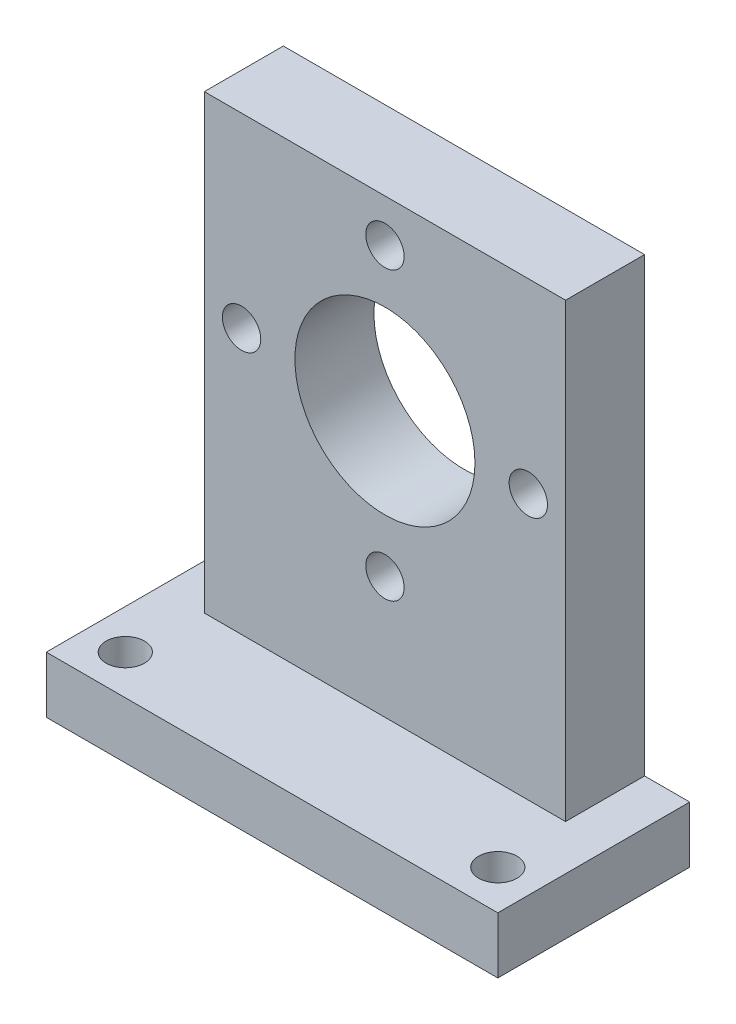
SolidWorks part; units mm, degrees
ref_plane "Front Plane" through (0, 0, 0) normal (0, 0, 1) x (1, 0, 0)
ref_plane "Top Plane" through (0, 0, 0) normal (0, 1, 0) x (1, 0, 0)
ref_plane "Right Plane" through (0, 0, 0) normal (1, 0, 0) x (0, 0, -1)
sketch "Sketch1" plane through (0, 0, 0) normal (0, 1, 0) x (1, 0, 0)
  line L1 (-20, 13.5) -> (20, 13.5)
  line L2 (-20, 13.5) -> (-20, -13.5)
  line L3 (-20, -13.5) -> (20, -13.5)
  line L4 (20, 13.5) -> (20, -13.5)
  line L5 (-20, 13.5) -> (20, -13.5) construction
  line L6 (-20, -13.5) -> (20, 13.5) construction
  line L7 (-16, 3.5) -> (16, 3.5)
  line L8 (-16, 3.5) -> (-16, -3.5)
  line L9 (-16, -3.5) -> (16, -3.5)
  line L10 (16, 3.5) -> (16, -3.5)
  line L11 (-16, 3.5) -> (16, -3.5) construction
  line L12 (-16, -3.5) -> (16, 3.5) construction
  point P0 (0, 0)
  point P6 (0, 0)
  dimension "D1" = 40
  dimension "D2" = 27
  dimension "D3" = 7
  dimension "D4" = 32
extrude "Boss-Extrude1" add sketch "Sketch1" along normal blind 5 contours L10 L7 L8 L9 | L2 L1 L4 L3 region at (0, 0, 0)
extrude "Boss-Extrude2" add sketch "Sketch1<3>" along normal blind 45 contours L10 L7 L8 L9 region at (0, 0, 0)
sketch "Sketch1<3>" plane through (0, 0, 0) normal (0, 1, 0) x (1, 0, 0) same geometry as "Sketch1"
sketch "Sketch2" plane through (0, 0, 3.5) normal (0, 0, 1) x (1, 0, 0)
  line L0 (-20, 5) -> (20, 5) construction
  circle A0 centre (0, 28.5) radius 7.9756
  dimension "D1" = 15.9512
  dimension "D2" = 23.5
extrude "Cut-Extrude1" cut sketch "Sketch2" against normal up to next
sketch "Sketch4" plane through (0, 0, 3.5) normal (0, 0, 1) x (1, 0, 0)
  line L0 (0, 45) -> (0, 28.5) construction
  line L1 (-16, 45) -> (16, 45) construction
  circle A0 centre (0, 41.2) radius 1.7
  circle A1 centre (0, 28.5) radius 7.9756 construction
  circle A2 centre (12.7, 28.5) radius 1.7
  circle A3 centre (0, 15.8) radius 1.7
  circle A4 centre (-12.7, 28.5) radius 1.7
  point P18 (0, 28.5)
  dimension "D2" = 3.4
  dimension "D1" = 12.7
  dimension "D3" = 4
extrude "Cut-Extrude2" cut sketch "Sketch4" against normal up to next
sketch "Sketch5" plane through (0, 5, 0) normal (0, 1, 0) x (1, 0, 0)
  line L1 (-20, 13.5) -> (20, 13.5) construction
  line L2 (-20, 13.5) -> (-20, -13.5) construction
  line L3 (-20, -13.5) -> (20, -13.5) construction
  line L4 (0, 13.5) -> (0, -13.5) construction
  circle A0 centre (-16.5, 10) radius 1.7
  circle A2 centre (-16.5, -10) radius 1.7
  circle A4 centre (16.5, -10) radius 1.7
  circle A5 centre (16.5, 10) radius 1.7
  dimension "D3" = 3.4
  dimension "D1" = 3.5
  dimension "D2" = 3.5
  dimension "D4" = 3.5
extrude "Cut-Extrude3" cut sketch "Sketch5" against normal up to next
sketch "Sketch7" plane through (0, 5, 0) normal (0, 1, 0) x (1, 0, 0)
  line L0 (-20, 13.5) -> (-20, -13.5) construction
  line L1 (-20, 3.5) -> (20, 3.5)
  line L2 (-20, 3.5) -> (-20, 13.5)
  line L3 (-20, 13.5) -> (20, 13.5)
  line L4 (20, 3.5) -> (20, 13.5)
  line L5 (-16, 3.5) -> (16, 3.5) construction
extrude "Cut-Extrude5" cut sketch "Sketch7" against normal up to next
sketch "Sketch8" plane through (0, 0, -3.5) normal (0, 0, -1) x (-1, 0, 0)
  line L0 (-12.7, 28.5) -> (-12.7, 2.5) construction
  line L1 (0, 0) -> (0, 13.0763) construction
  line L5 (-20, 5) -> (-20, 0) construction
  circle A0 centre (-12.7, 2.5) radius 1.7
  circle A1 centre (12.7, 2.5) radius 1.7
  circle A2 centre (-12.7, 28.5) radius 1.7 construction
  point P9 (-20, 2.5)
extrude "Cut-Extrude6" cut sketch "Sketch8" against normal blind 6.35
